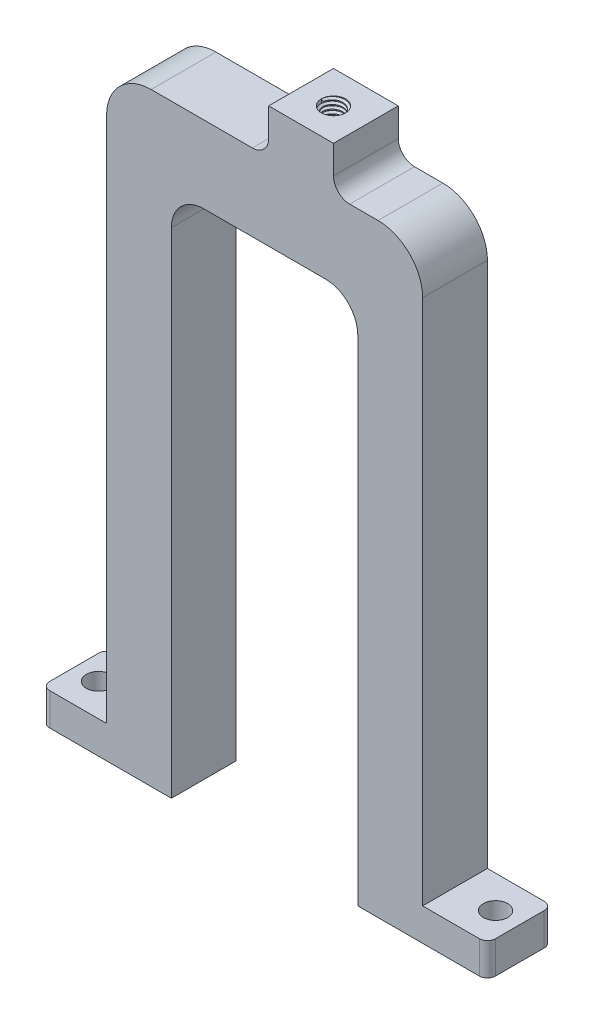
SolidWorks part; units mm, degrees
ref_plane "Front Plane" through (0, 0, 0) normal (0, 0, 1) x (1, 0, 0)
ref_plane "Top Plane" through (0, 0, 0) normal (0, 1, 0) x (1, 0, 0)
ref_plane "Right Plane" through (0, 0, 0) normal (1, 0, 0) x (0, 0, -1)
sketch "Sketch1" plane through (0, 0, 0) normal (0, 0, 1) x (1, 0, 0)
  line L0 (-15, 0) -> (15, 0)
  line L1 (23, -8) -> (23, -130)
  line L2 (23, -130) -> (55, -130)
  line L3 (55, -130) -> (55, -122)
  line L4 (55, -122) -> (39, -122)
  line L5 (39, -122) -> (39, 8)
  line L6 (28, 19) -> (21, 19)
  line L7 (17, 23) -> (17, 30)
  line L10 (-3, 19) -> (-28, 19)
  line L11 (0, 101.2326) -> (0, -100.4706) construction
  line L12 (-29.6471, 19) -> (-17, 19)
  line L13 (-23, -8) -> (-23, -130)
  line L14 (-39, -122) -> (-39, 8)
  line L15 (-55, -122) -> (-39, -122)
  line L16 (-55, -130) -> (-55, -122)
  line L17 (-23, -130) -> (-55, -130)
  line L18 (17, 30) -> (1, 30)
  line L19 (1, 30) -> (1, 23)
  line L21 (-3, 19) -> (-4, 19)
  arc A0 (23, -8) -> (15, 0) centre (15, -8) ccw
  arc A1 (-23, -8) -> (-15, 0) centre (-15, -8) cw
  arc A2 (-39, 8) -> (-28, 19) centre (-28, 8) cw
  arc A3 (39, 8) -> (28, 19) centre (28, 8) ccw
  arc A5 (21, 19) -> (17, 23) centre (21, 23) cw
  arc A6 (-3, 19) -> (1, 23) centre (-3, 23) ccw
  point P24 (-15, -8)
  point P27 (0, 0)
  point P37 (17, 19)
  dimension "D4" = 8
  dimension "D6" = 122
  dimension "D13" = 4
  dimension "D14" = 4
  dimension "D1" = 32
  dimension "D2" = 16
  dimension "D3" = 8
  dimension "D5" = 23
  dimension "D8" = 19
  dimension "D9" = 1
  dimension "D10" = 11
  dimension "D11" = 16
  dimension "D12" = 11
extrude "Boss-Extrude1" add sketch "Sketch1" along normal blind 16 contours L11 A6 L10 A2 L14 L15 L16 L17 L13 A1 L0 | A6 L11 L0 A0 L1 L2 L3 L4 L5 A3 L6 A5 L7 L18 L19 region at (-28.6891, -49.2572, 0) region at (27.5574, -44.997, 0)
sketch "Sketch2" plane through (0, 30, 0) normal (0, 1, 0) x (1, 0, 0)
  line L0 (17, -16) -> (1, -16) construction
  line L5 (17, -16) -> (17, 0) construction
  circle A0 centre (9, -8) radius 3
  dimension "D1" = 6
  dimension "D2" = 8
  dimension "D3" = 8
extrude "Cut-Extrude1" cut sketch "Sketch2" against normal blind 15
fillet "Fillet1" radius 2 4 edges at (55, -126, 0) (55, -126, 16) (-55, -126, 0) (-55, -126, 16)
sketch "Sketch3" plane through (0, -122, 0) normal (0, 1, 0) x (1, 0, 0)
  line L0 (-55, -14) -> (-55, -2) construction
  line L1 (-53, 0) -> (-39, 0) construction
  line L3 (0, 10.2917) -> (0, -28.2435) construction
  circle A0 centre (-49, -8) radius 3
  circle A1 centre (49, -8) radius 3
  dimension "D1" = 6
  dimension "D2" = 6
  dimension "D3" = 8
extrude "Cut-Extrude2" cut sketch "Sketch3" against normal through all
thread "Thread1" pitch 1 method extrude profile "Thread Profile1" start angle 0, offset 0, length 15, pitch 1, diameter 6
ref_plane "Plane1" through (6, 30, 8) normal (0, 0, 1) x (-1, 0, 0)
sketch "Thread Profile1" plane through (6, 30, 8) normal (0, 0, 1) x (-1, 0, 0)
  line L0 (0, 0) -> (0, 1) construction
  line L11 (0, 0) -> (0, 0.875)
  line L12 (0, 0.875) -> (-0.5413, 0.5625)
  line L13 (-0.5413, 0.5625) -> (-0.5413, 0.3125)
  line L15 (-0.5413, 0.3125) -> (0, 0)
  line L17 (-0.5413, 0.4375) -> (0, 0.4375) construction
  point P2 (0, 0)
  dimension "Pitch" = 1
  dimension "Profile_Angle" = 60
  dimension "Profile_Land" = 0.25
  dimension "Profile_Height" = 0.5413
